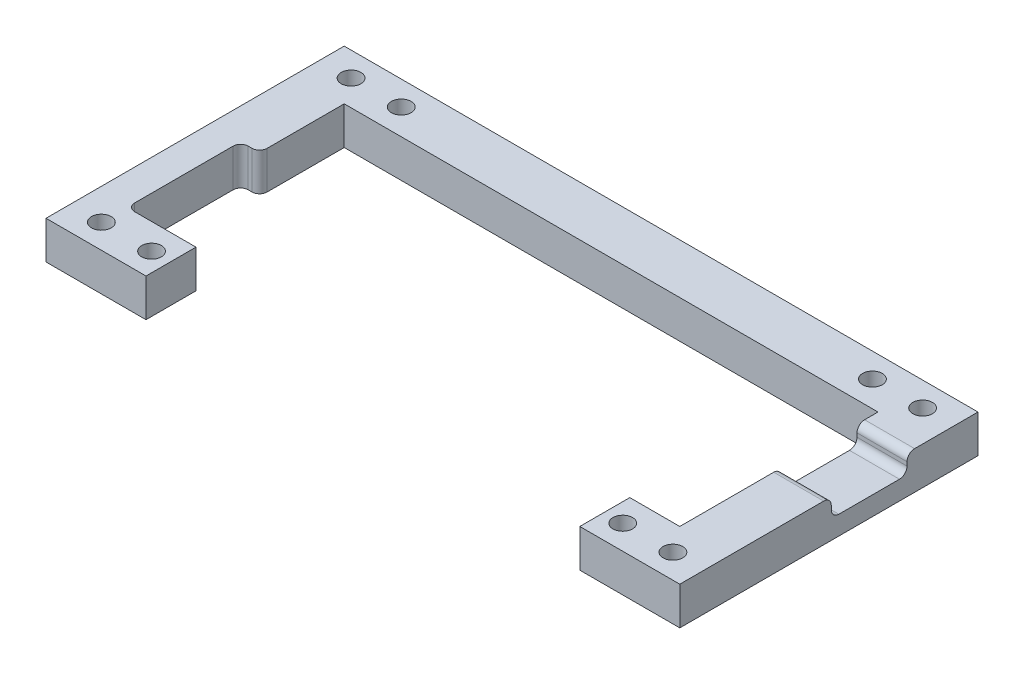
SolidWorks part; units mm, degrees
ref_plane "Front Plane" through (0, 0, 0) normal (0, 0, 1) x (1, 0, 0)
ref_plane "Top Plane" through (0, 0, 0) normal (0, 1, 0) x (1, 0, 0)
ref_plane "Right Plane" through (0, 0, 0) normal (1, 0, 0) x (0, 0, -1)
sketch "Sketch1" plane through (0, 0, 0) normal (0, 1, 0) x (1, 0, 0)
  line L0 (181.4198, 36.9979) -> (75.1552, 36.9979) construction
  line L1 (75.1552, 11.9979) -> (83.5372, 11.9979)
  line L2 (75.1552, 11.9979) -> (75.1552, 61.9979)
  line L3 (75.1552, 61.9979) -> (83.5372, 61.9979)
  line L4 (83.5372, 11.9979) -> (83.5372, 61.9979)
  line L5 (83.5372, 61.9979) -> (91.9192, 61.9979)
  line L6 (83.5372, 61.9979) -> (83.5372, 53.6159)
  line L7 (83.5372, 53.6159) -> (91.9192, 53.6159)
  line L8 (167.7876, 16.0648) -> (186.7138, 16.0648) construction
  line L9 (83.5372, 11.9979) -> (91.9192, 11.9979)
  line L10 (83.5372, 11.9979) -> (83.5372, 20.3799)
  line L11 (83.5372, 20.3799) -> (91.9192, 20.3799)
  line L12 (91.9192, 11.9979) -> (91.9192, 20.3799)
  line L13 (75.1552, 61.9979) -> (181.4198, 61.9979)
  line L17 (181.4198, 61.9979) -> (173.0378, 61.9979)
  line L18 (181.4198, 61.9979) -> (181.4198, 11.9979)
  line L19 (181.4198, 11.9979) -> (173.0378, 11.9979)
  line L20 (173.0378, 61.9979) -> (173.0378, 11.9979)
  line L21 (173.0378, 61.9979) -> (164.6558, 61.9979)
  line L22 (173.0378, 61.9979) -> (173.0378, 53.6159)
  line L23 (173.0378, 53.6159) -> (164.6558, 53.6159)
  line L25 (173.0378, 11.9979) -> (164.6558, 11.9979)
  line L26 (173.0378, 11.9979) -> (173.0378, 20.3799)
  line L27 (173.0378, 20.3799) -> (164.6558, 20.3799)
  line L28 (164.6558, 11.9979) -> (164.6558, 20.3799)
  line L29 (128.2875, 61.9979) -> (128.2875, -9.1774) construction
  line L30 (164.6558, 53.6159) -> (91.9192, 53.6159)
  circle A0 centre (167.7876, 57.931) radius 1.651
  circle A1 centre (167.7876, 16.0648) radius 1.651
  circle A2 centre (88.7875, 16.0648) radius 1.651
  circle A3 centre (88.7875, 57.931) radius 1.651
  circle A4 centre (176.2028, 16.0648) radius 1.651
  circle A5 centre (80.3722, 16.0648) radius 1.651
  circle A6 centre (80.3722, 57.931) radius 1.651
  circle A7 centre (176.2028, 57.931) radius 1.651
  point P32 (91.9192, 16.1889)
  point P34 (88.7875, 57.931)
  point P35 (88.7875, 16.0648)
  dimension "D15" = 3.302
  dimension "D16" = 3.1342
  dimension "D6" = 79.0001
  dimension "D18" = 3.302
  dimension "D2" = 47.9153
  dimension "D1" = 8.382
  dimension "D3" = 50
  dimension "D4" = 8.382
  dimension "D5" = 50
  dimension "D7" = 8.382
  dimension "D8" = 8.382
  dimension "D9" = 8.382
  dimension "D10" = 8.382
  dimension "D11" = 8.382
  dimension "D12" = 8.382
  dimension "D13" = 8.382
  dimension "D14" = 8.382
  dimension "D17" = 3.1317
extrude "Boss-Extrude1" add sketch "Sketch1" along normal blind 6.35 contours L1 L4 L3 L2 | L13 L3 L5 | L13 L20 L19 L18 | L13 L23 L20 | L28 L25 L20 L27 | L9 L12 L11 L4 | L5 L4 L7 | L1 L4 L2 | L20 L19 L18 region at (79.3025, 0, -36.9979) region at (83.6557, 0, -16.1889) region at (128.2875, 0, -57.804) region at (177.2725, 0, -36.9979) region at (172.9193, 0, -16.1889)
sketch "Sketch2" plane through (181.4198, 0, 0) normal (1, 0, 0) x (0, 0, -1)
  line L0 (61.9979, 6.35) -> (11.9979, 6.35) construction
  line L1 (37.3979, 6.35) -> (50.0979, 6.35)
  line L2 (37.3979, 6.35) -> (37.3979, 3.175)
  line L3 (37.3979, 3.175) -> (50.0979, 3.175)
  line L4 (50.0979, 6.35) -> (50.0979, 3.175)
  line L5 (11.9979, 6.35) -> (11.9979, 0) construction
  dimension "D1" = 25.4
  dimension "D2" = 12.7
  dimension "D3" = 3.175
extrude "Cut-Extrude7" cut sketch "Sketch2" against normal blind 8.89 contours L2 L3 L4 L1
fillet "Fillet2" radius 1.27 4 edges at (177.2288, 3.175, -37.3979) (177.2288, 6.35, -37.3979) (177.2288, 6.35, -50.0979) (177.2288, 3.175, -50.0979)
sketch "Sketch4" plane through (0, 6.35, 0) normal (0, 1, 0) x (1, 0, 0)
  line L1 (83.5372, 20.3799) -> (80.3622, 20.3799)
  line L2 (83.5372, 20.3799) -> (83.5372, 39.4299)
  line L3 (83.5372, 39.4299) -> (80.3622, 39.4299)
  line L4 (80.3622, 20.3799) -> (80.3622, 39.4299)
  dimension "D1" = 3.175
  dimension "D2" = 19.05
extrude "Cut-Extrude8" cut sketch "Sketch4" against normal through all
fillet "Fillet3" radius 1.27 3 edges at (80.3622, 3.175, -20.3799) (80.3622, 3.175, -39.4299) (83.5372, 3.175, -39.4299)
